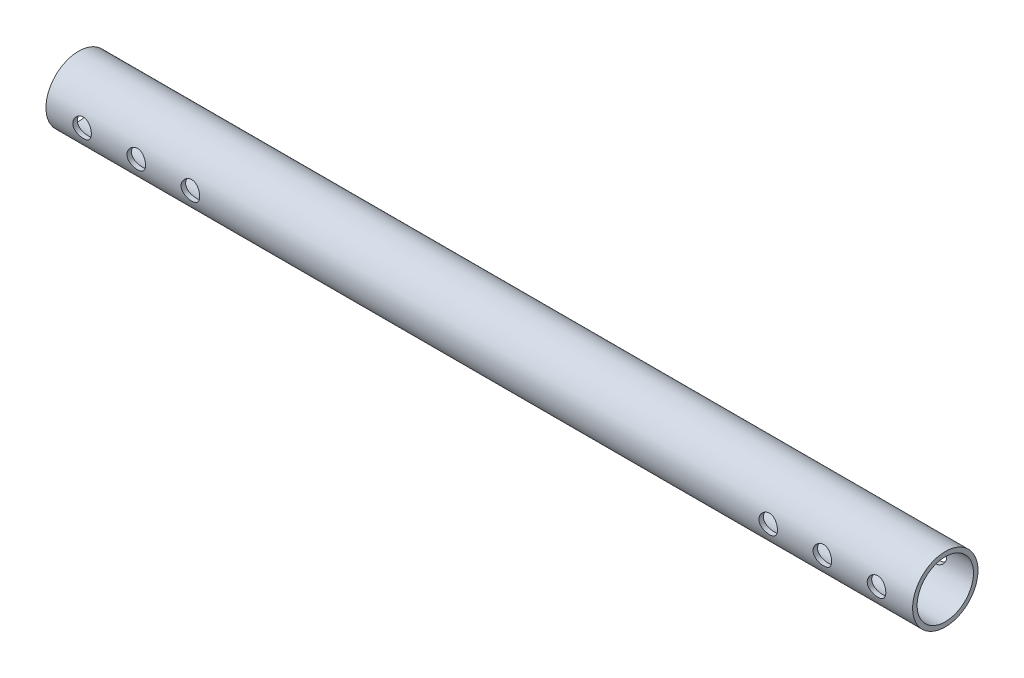
SolidWorks part; units mm, degrees
ref_plane "Front Plane" through (0, 0, 0) normal (0, 0, 1) x (1, 0, 0)
ref_plane "Top Plane" through (0, 0, 0) normal (0, 1, 0) x (1, 0, 0)
ref_plane "Right Plane" through (0, 0, 0) normal (1, 0, 0) x (0, 0, -1)
sketch "Sketch1" plane through (0, 0, 0) normal (1, 0, 0) x (0, 0, -1)
  circle A0 centre (0, 0) radius 11.5
  circle A1 centre (0, 0) radius 9.9125
  dimension "D1" = 1.5875
extrude "Boss-Extrude1" add sketch "Sketch1" along normal blind 304.8
ref_plane "Plane1" through (0, 0, 10) normal (0, 0, 1) x (1, 0, 0)
sketch "Sketch2" plane through (0, 0, 10) normal (0, 0, 1) x (1, 0, 0)
  line L0 (0, 0) -> (304.8, 0) construction
  line L1 (304.8, -11.5) -> (304.8, 11.5) construction
  line L2 (152.4, 11.5) -> (152.4, -11.5) construction
  line L3 (304.8, 11.5) -> (0, 11.5) construction
  circle A0 centre (12.7, 0) radius 3.2639
  circle A1 centre (31.75, 0) radius 3.2639
  circle A2 centre (50.8, 0) radius 3.2639
  circle A3 centre (292.1, 0) radius 3.2639
  circle A4 centre (273.05, 0) radius 3.2639
  circle A5 centre (254, 0) radius 3.2639
  point P15 (152.4, 0)
  dimension "D1" = 12.7
  dimension "D2" = 3
extrude "Cut-Extrude1" cut sketch "Sketch2" against normal through all and the other way through all
equation "\"1f\"=10"
